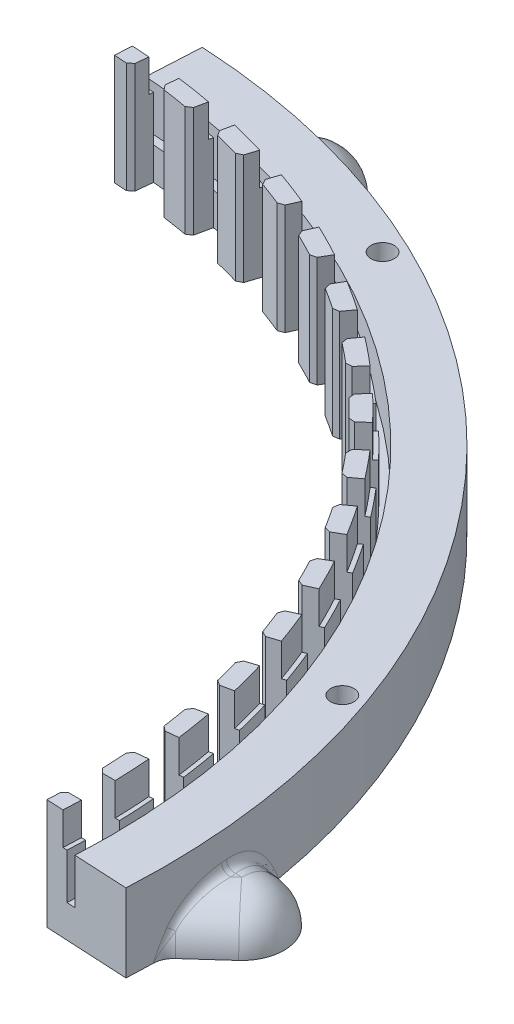
SolidWorks part; units mm, degrees
material "ABS"
ref_plane "Front" through (0, 0, 0) normal (0, 0, 1) x (1, 0, 0)
ref_plane "Top" through (0, 0, 0) normal (0, 1, 0) x (1, 0, 0)
ref_plane "Right" through (0, 0, 0) normal (1, 0, 0) x (0, 0, -1)
sketch "Sketch1" plane through (0, 0, 0) normal (0, 0, 1) x (1, 0, 0)
  line L0 (0, 0) -> (0, 73.8032) construction
  line L1 (-152.75, 0) -> (-172.5, 0)
  line L2 (-172.5, 0) -> (-172.5, 18.46)
  line L4 (-159.75, 18.46) -> (-159.75, 7.71)
  line L5 (-159.75, 7.71) -> (-157.75, 7.71)
  line L6 (-157.75, 7.71) -> (-157.75, 18.46)
  line L7 (-157.75, 18.46) -> (-156.75, 18.46)
  line L8 (-152.75, 26.17) -> (-152.75, 0)
  line L9 (-158.75, 7.71) -> (-158.75, 50.9792) construction
  line L10 (-156.75, 18.46) -> (-156.75, 26.17)
  line L11 (-156.75, 26.17) -> (-152.75, 26.17)
  line L13 (-159.75, 18.46) -> (-172.5, 18.46)
  point P6 (-152.75, 13.085)
  point P19 (-157.75, 13.085)
  dimension "D1" = 158.75
  dimension "D2" = 2
  dimension "D3" = 10.75
  dimension "D6" = 1
  dimension "D7" = 305.5
  dimension "D9" = 345
  dimension "D11" = 26.17
revolve "Revolve1" add sketch "Sketch1" angle 360 about L0
sketch "Sketch2" plane through (0, 0, 0) normal (0, 0, 1) x (1, 0, 0)
  line L0 (156.75, 26.17) -> (-156.75, 26.17) construction
  line L1 (159.75, 7.71) -> (-159.75, 7.71) construction
  line L2 (-4, 26.17) -> (4, 26.17)
  line L3 (-4, 26.17) -> (-4, 7.71)
  line L4 (-4, 7.71) -> (4, 7.71)
  line L5 (4, 26.17) -> (4, 7.71)
  point P4 (0, 7.71)
  dimension "D1" = 8
extrude "Cut-Extrude1" cut sketch "Sketch2" against normal up to surface (157.6993 mm away)
pattern_circular "CirPattern1" count 60 every 6 about axis through (0, 0, 0) along (0, 1, 0) of "Cut-Extrude1"
sketch "Sketch6" plane through (0, 0, 0) normal (0, 1, 0) x (1, 0, 0)
  line L0 (0, 0) -> (-227.339, 0) construction
  line L1 (-172.4275, -5) -> (-167.0659, -5)
  line L2 (-164.9008, -1.25) -> (-166.3442, 1.25)
  line L3 (-164.1791, 5) -> (-159.6759, 5)
  line L4 (-157.5108, 1.25) -> (-158.9542, -1.25)
  line L5 (-156.7892, -5) -> (-151.4275, -5)
  line L6 (-167.0659, -4.5) -> (-172.4413, -4.5)
  line L7 (-164.9008, -1.25) -> (-162.7358, -5) construction
  line L8 (-167.0659, -5) -> (-162.7358, -5) construction
  line L9 (-156.7892, -4.5) -> (-151.4275, -4.5)
  line L10 (-164.1791, 5.5) -> (-159.6759, 5.5)
  line L11 (-164.1791, 5) -> (-168.5093, 5) construction
  line L12 (-166.3442, 1.25) -> (-168.5093, 5) construction
  line L13 (-159.6759, 5) -> (-155.3458, 5) construction
  line L14 (-157.5108, 1.25) -> (-155.3458, 5) construction
  line L15 (-156.7892, -5) -> (-161.1193, -5) construction
  line L16 (-158.9542, -1.25) -> (-161.1193, -5) construction
  line L17 (-166.7772, 1) -> (-165.3338, -1.5)
  line L18 (-157.0778, 1) -> (-158.5212, -1.5)
  line L19 (-172.4413, -4.5) -> (-172.4275, -5)
  line L20 (-151.4275, -4.5) -> (-151.4275, -5)
  line L22 (-179.9733, 22.1061) -> (-143.3935, 22.1061)
  line L24 (-179.8648, -22.9723) -> (-143.2573, -22.9723)
  arc A0 (-179.8648, -22.9723) -> (-179.9733, 22.1061) centre (0, 0) ccw
  arc A1 (-166.3442, 1.25) -> (-164.1791, 5) centre (-164.1791, 2.5) cw
  arc A2 (-159.6759, 5) -> (-157.5108, 1.25) centre (-159.6759, 2.5) cw
  arc A3 (-158.9542, -1.25) -> (-156.7892, -5) centre (-156.7892, -2.5) ccw
  arc A4 (-164.9008, -1.25) -> (-167.0659, -5) centre (-167.0659, -2.5) cw
  arc A5 (-156.7892, -4.5) -> (-158.5212, -1.5) centre (-156.7892, -2.5) cw
  arc A6 (-167.0659, -4.5) -> (-165.3338, -1.5) centre (-167.0659, -2.5) ccw
  arc A7 (-159.6759, 5.5) -> (-157.0778, 1) centre (-159.6759, 2.5) cw
  arc A8 (-164.1791, 5.5) -> (-166.7772, 1) centre (-164.1791, 2.5) ccw
  arc A9 (-143.2573, -22.9723) -> (-143.3935, 22.1061) centre (0, 0) ccw
  point P10 (-158.2325, 0)
  point P20 (-161.1193, -5)
  point P35 (-163.6018, -4.5)
  dimension "D5" = 2.5
  dimension "D10" = 2
  dimension "D11" = 3
  dimension "D1" = 60
  dimension "D2" = 60
  dimension "D3" = 10
  dimension "D4" = 21
  dimension "D6" = 0.5
  dimension "D7" = 0.5
  dimension "D8" = 0.5
  dimension "D9" = 0.5
extrude "Cut-Extrude2" [suppressed] cut sketch "Sketch6" against normal mid plane 50.8 contours L1 A4 L2 A1 L3 A2 L4 A3 L5 L20 L9 A5 L18 A7 L10 A8 L17 A6 L6 L19
sketch "Sketch7" plane through (0, 0, 0) normal (0, 1, 0) x (1, 0, 0)
  line L0 (0, 0) -> (123.0455, 123.0455) construction
  line L1 (106.6477, 106.6477) -> (116.0362, 116.0362) construction
  line L2 (0, 0) -> (9.8423, 187.8015)
  line L3 (116.0362, 116.0362) -> (118.8646, 113.2078) construction
  line L4 (119.8546, 119.8546) -> (122.683, 117.0262) construction
  line L5 (122.683, 117.0262) -> (118.8646, 113.2078) construction
  line L6 (116.0009, 115.9302) -> (106.683, 106.6123) construction
  line L7 (116.0009, 115.9302) -> (118.8293, 113.1017) construction
  line L8 (118.8293, 113.1017) -> (122.7891, 117.0615) construction
  line L9 (122.7891, 117.0615) -> (119.9607, 119.89) construction
  line L10 (119.9607, 119.89) -> (123.0809, 123.0102) construction
  line L11 (0, 0) -> (187.8015, -9.8423)
  line L12 (123.0809, 123.0102) -> (123.0455, 123.0455) construction
  line L13 (106.683, 106.6123) -> (106.6477, 106.6477) construction
  line L14 (119.8546, 119.8546) -> (123.0455, 123.0455) construction
  line L15 (0, 0) -> (0, 201.7846) construction
  line L97 (36.045, 134.5218) -> (39.4815, 147.3469) [skipped]
  line L98 (39.5039, 147.2373) -> (36.0933, 134.5089) [skipped]
  line L99 (39.5039, 147.2373) -> (43.3676, 146.202) [skipped]
  line L100 (39.4815, 147.3469) -> (43.3452, 146.3116) [skipped]
  line L101 (44.7428, 151.5276) -> (43.3452, 146.3116) [skipped]
  line L102 (43.3676, 146.202) -> (44.817, 151.6112) [skipped]
  line L103 (40.8791, 152.5629) -> (44.7428, 151.5276) [skipped]
  line L104 (44.817, 151.6112) -> (40.9533, 152.6465) [skipped]
  line L105 (40.9533, 152.6465) -> (42.0953, 156.9088) [skipped]
  line L106 (40.8791, 152.5629) -> (42.0471, 156.9217) [skipped]
  line L107 (190.7733, 117.0706) -> (187.6115, 117.9179) [skipped]
  line L108 (164.7318, 100.0403) -> (162.2106, 100.7159) [skipped]
  line L109 (161.2041, 52.3784) -> (165.4959, 53.7729) [skipped]
  line L110 (161.3146, 52.3617) -> (165.5113, 53.7253) [skipped]
  line L111 (157.2248, 46.827) -> (162.5507, 48.5575) [skipped]
  line L112 (162.4401, 48.5742) -> (157.3044, 46.9055) [skipped]
  line L113 (161.2041, 52.3784) -> (162.4401, 48.5742) [skipped]
  line L114 (162.5507, 48.5575) -> (161.3146, 52.3617) [skipped]
  line L115 (156.0684, 50.7097) -> (157.3044, 46.9055) [skipped]
  line L116 (155.9887, 50.6312) -> (157.2248, 46.827) [skipped]
  line L117 (155.9887, 50.6312) -> (143.4562, 46.5592) [skipped]
  line L118 (143.4408, 46.6067) -> (156.0684, 50.7097) [skipped]
  line L119 (165.5113, 53.7254) -> (165.4959, 53.7729) [skipped]
  line L120 (143.4562, 46.5592) -> (143.4408, 46.6067) [skipped]
  arc A0 (9.8423, 187.8015) -> (187.8015, -9.8423) centre (0, 0) ccw
  point P6 (8.1708, 8.1708)
  point P21 (0, 0)
  point P22 (10.9898, 3.5708)
  point P29 (19.3324, -11.1616)
  point P31 (0, 0)
  point P36 (0, 0)
  point P49 (0, 0)
  point P53 (0, 0)
  point P63 (0, 0)
  point P71 (0, 0)
  point P74 (0, 0)
  dimension "D3" = 2
  dimension "D4" = 3
  dimension "D1" = 2
  dimension "D2" = 4
extrude "Cut-Extrude3" cut sketch "Sketch7" against normal mid plane 60.8
sketch "Sketch9" plane through (0, 0, 0) normal (0, 1, 0) x (1, 0, 0)
  line L0 (12.506, 157.2535) -> (11.8051, 150.5851)
  line L1 (20.4622, 156.4173) -> (19.7613, 149.7489)
  line L2 (11.8051, 150.5851) -> (19.7613, 149.7489)
  line L3 (11.9832, 152.2792) -> (12.4014, 156.2587) construction
  line L4 (20.3576, 155.4224) -> (19.9393, 151.443) construction
  arc A0 (20.4622, 156.4173) -> (12.506, 157.2535) centre (0, 0) ccw
  arc A2 (12.506, 157.2535) -> (8.256, 157.5338) centre (0, 0) ccw construction
extrude "Cut-Extrude5" cut sketch "Sketch9" along normal blind 10
sketch3d "3DSketch1"
  line L0 (0, 0, 0) -> (0, 55.3849, 0) construction
pattern_circular "CirPattern2" count 60 over 360 about axis through (0, 0, 0) along (0, 1, 0) of "Cut-Extrude5"
chamfer "Chamfer3" distance 1 angle 45 30 edges at (143.988, 13.085, -50.9904) (141.1232, 13.085, -58.4535) (137.8693, 13.085, -65.7619) (134.24, 13.085, -72.8847) (130.24, 13.085, -79.8129) (125.8861, 13.085, -86.5173) (121.1838, 13.085, -92.9895) (116.153, 13.085, -99.2021) (110.7999, 13.085, -105.1472) (105.1472, 13.085, -110.7999) (99.2021, 13.085, -116.153) (92.9895, 13.085, -121.1838) (79.8129, 13.085, -130.24) (86.5173, 13.085, -125.8861) (72.8847, 13.085, -134.24) (65.7619, 13.085, -137.8693) (58.4535, 13.085, -141.1232) (50.9904, 13.085, -143.988) (43.3819, 13.085, -146.4601) (35.6602, 13.085, -148.5292) (27.835, 13.085, -150.1925) (19.9393, 13.085, -151.443) (11.9832, 13.085, -152.2792) (152.2792, 13.085, -11.9832) (150.1925, 13.085, -27.835) (146.4601, 13.085, -43.3819) (152.6976, 13.085, -4) (151.443, 13.085, -19.9393) (148.5292, 13.085, -35.6602) (152.6976, 13.085, 4)
hole_wizard "#6 Clearance Hole1" positions "Sketch10" profile "Sketch11" hole size "#6" standard "ANSI Inch" end condition through all
sketch "Sketch10" plane through (0, 18.46, 0) normal (0, 1, 0) x (1, 0, 0)
  line L0 (9.028, 172.2636) -> (0, 0) construction
  line L1 (0, 0) -> (172.2636, -9.028) construction
  line L2 (72.3259, 151.6343) -> (0, 0) construction
  line L3 (0, 0) -> (158.3638, 56.0796) construction
  line L4 (79.1819, 28.0398) -> (86.1318, -4.514) construction
  line L5 (36.1629, 75.8172) -> (4.514, 86.1318) construction
  circle A0 centre (0, 0) radius 168 construction
  point P13 (72.3259, 151.6343)
  point P16 (158.3638, 56.0796)
  dimension "D3" = 336
  dimension "D1" = 45
sketch "Sketch11" plane through (158.3638, 18.46, -56.0796) normal (1, 0, 0) x (0, 0, 1)
  line L0 (0, 0) -> (0, 18.46)
  line L1 (0, 18.46) -> (2.75, 18.46)
  line L2 (2.75, 18.46) -> (2.75, 0)
  line L5 (2.75, 0) -> (0, 0)
  line L11 (0, -6.35) -> (0, 107.95) construction
  dimension "Thru Hole Dia." = 5.5
  dimension "Thru Hole Depth" = 18.46
sketch "Sketch13" [suppressed] plane through (0, 18.46, 0) normal (0, 1, 0) x (1, 0, 0)
  line L0 (64.2908, 155.2118) -> (0, 0) construction
  line L1 (0, 0) -> (123.547, 123.547) construction
  line L2 (155.2118, 64.2908) -> (0, 0) construction
  line L3 (32.1454, 77.6059) -> (61.7735, 61.7735) construction
  line L4 (61.7735, 61.7735) -> (77.6059, 32.1454) construction
  line L5 (115.0617, 110.8191) -> (125.6683, 121.4257)
  line L6 (110.8191, 115.0617) -> (121.4257, 125.6683)
  line L7 (116.1224, 120.365) -> (120.365, 116.1224) construction
  line L8 (121.4257, 125.6683) -> (125.6683, 121.4257)
  arc A0 (159.75, 0) -> (0, 159.75) centre (0, 0) ccw construction
  arc A1 (115.0617, 110.8191) -> (110.8191, 115.0617) centre (0, 0) ccw
  point P15 (118.2437, 118.2437)
  dimension "D1" = 6
  dimension "D2" = 15
extrude "Cut-Extrude6" [suppressed] cut sketch "Sketch13" against normal blind 15
sketch "Sketch14" [suppressed] plane through (0, 0, 0) normal (0, 1, 0) x (1, 0, 0)
  line L0 (119.8362, 124.0788) -> (121.9575, 126.2001)
  line L1 (124.0788, 119.8362) -> (126.2001, 121.9575)
  line L2 (119.8362, 124.0788) -> (110.8191, 115.0617) construction
  line L3 (115.0617, 110.8191) -> (124.0788, 119.8362) construction
  line L4 (119.8362, 124.0788) -> (124.0788, 119.8362)
  arc A0 (121.9575, 126.2001) -> (126.2001, 121.9575) centre (0, 0) cw
  arc A1 (119.8362, 124.0788) -> (0, 172.5) centre (0, 0) ccw construction
  dimension "D1" = 3
extrude "Boss-Extrude1" [suppressed] add sketch "Sketch14" along normal up to surface (3.46 mm away)
sketch "Sketch15" [suppressed] plane through (0, 18.46, 0) normal (0, 1, 0) x (1, 0, 0)
  line L0 (0, 0) -> (112.9603, 112.9603) construction
  line L1 (143.4285, 95.8359) -> (0, 0) construction
  line L2 (141.6027, 91.3686) -> (144.9285, 93.5909)
  line L3 (141.9285, 98.0808) -> (138.6026, 95.8586)
  line L4 (141.9285, 98.0808) -> (144.9285, 93.5909)
  line L5 (138.6026, 95.8586) -> (135.9359, 99.8496)
  line L6 (135.9359, 99.8496) -> (130.1156, 95.9606)
  line L7 (130.1156, 95.9606) -> (138.4491, 83.4886)
  line L8 (138.4491, 83.4886) -> (144.2694, 87.3776)
  line L9 (144.2694, 87.3776) -> (141.6027, 91.3686)
  line L10 (95.8359, 143.4285) -> (0, 0) construction
  line L11 (87.3776, 144.2694) -> (91.3686, 141.6027)
  line L12 (83.4886, 138.4491) -> (87.3776, 144.2694)
  line L13 (95.9606, 130.1156) -> (83.4886, 138.4491)
  line L14 (99.8496, 135.9359) -> (95.9606, 130.1156)
  line L15 (95.8586, 138.6026) -> (99.8496, 135.9359)
  line L16 (98.0808, 141.9285) -> (93.5909, 144.9285)
  line L17 (98.0808, 141.9285) -> (95.8586, 138.6026)
  line L18 (91.3686, 141.6027) -> (93.5909, 144.9285)
  arc A0 (115.0617, 110.8191) -> (110.8191, 115.0617) centre (0, 0) ccw construction
  arc A4 (172.5, 0) -> (124.0788, 119.8362) centre (0, 0) ccw construction
  point P9 (143.4285, 95.8359)
  point P10 (134.2823, 89.7246)
  dimension "D1" = 5.4
  dimension "D2" = 4
  dimension "D3" = 7
  dimension "D4" = 15
  dimension "D5" = 11.25
extrude "Cut-Extrude7" [suppressed] cut sketch "Sketch15" against normal blind 5
sketch "Sketch16" plane through (0, 0, 0) normal (0, 1, 0) x (1, 0, 0)
  line L2 (0, 0) -> (108.0106, 108.0106) construction
  line L3 (182.0129, 7.9072) -> (174.1306, 0.81)
  line L4 (26.8894, 180.1892) -> (19.0071, 173.092)
  arc A1 (172.2636, -9.028) -> (9.028, 172.2636) centre (0, 0) ccw construction
  arc A2 (172.4769, -2.8239) -> (169.9626, 29.478) centre (0, 0) ccw
  arc A3 (47.0824, 165.9503) -> (15.2203, 171.8272) centre (0, 0) ccw
  arc A4 (110.0878, 105.8926) -> (105.8926, 110.0878) centre (0, 0) ccw construction
  arc A5 (174.1306, 0.81) -> (172.4769, -2.8239) centre (177.4762, -2.9058) ccw
  arc A7 (182.0129, 7.9072) -> (175.0332, 25.3345) centre (175.3215, 15.3386) ccw
  arc A8 (169.9626, 29.478) -> (175.0332, 25.3345) centre (174.8891, 30.3324) ccw
  arc A11 (15.2203, 171.8272) -> (19.0071, 173.092) centre (15.6615, 176.8077) ccw
  arc A12 (43.4917, 171.4262) -> (26.8894, 180.1892) centre (33.5807, 172.7578) ccw
  arc A13 (43.4917, 171.4262) -> (47.0824, 165.9503) centre (48.4471, 170.7604) ccw
extrude "Boss-Extrude2" add sketch "Sketch16" along normal blind 10
fillet "Fillet1" radius 10 8 edges at (172.9253, 10, 0.8348) (178.0717, 10, -4.3586) (171.7253, 10, -26.4607) (44.2659, 10, -168.0187) (17.2454, 10, -172.0652) (22.9483, 10, -176.6406) (184.6047, 10, -19.0565) (38.2486, 10, -181.6015)
fillet "Fillet2" radius 2 8 edges at (170.9874, 7.5893, -22.7939) (171.9287, 10, -14.0271) (172.4184, 8.3422, -5.3045) (40.5421, 7.5893, -167.6681) (31.9217, 10, -169.5207) (38.969, -1.3977, -168.0407) (25.3782, 9.2073, -170.623)
